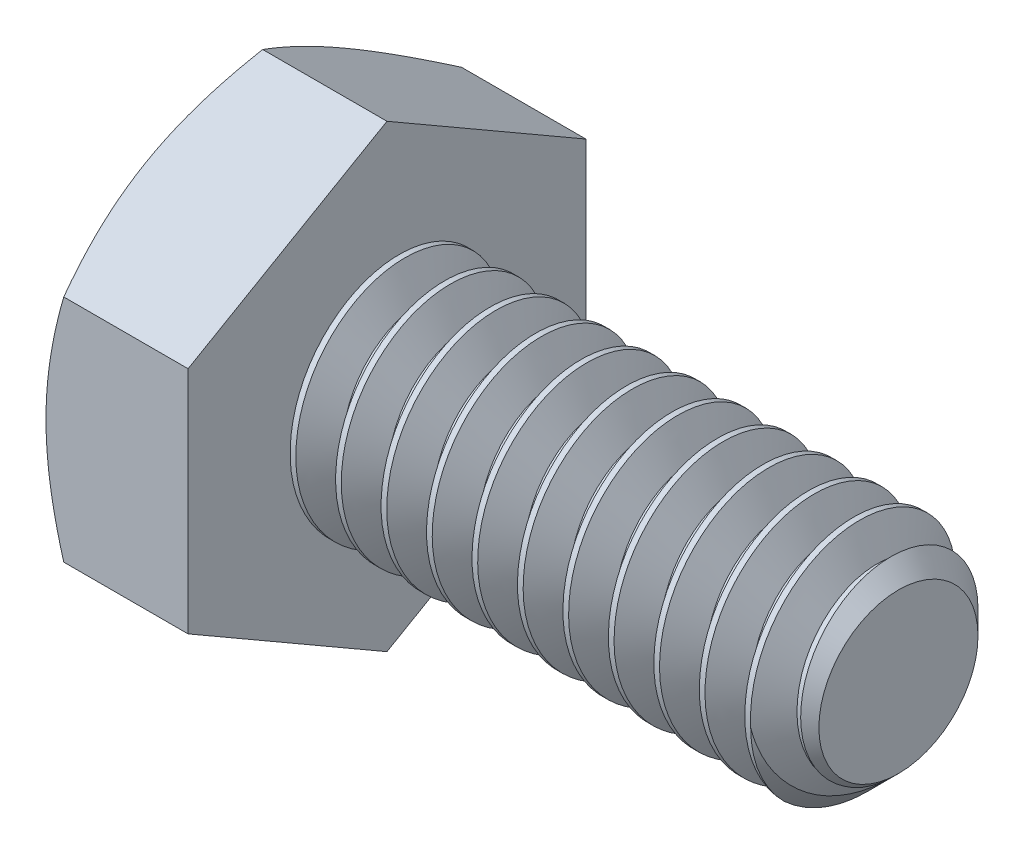
SolidWorks part; units mm, degrees
ref_plane "Front Plane" through (0, 0, 0) normal (0, 0, 1) x (1, 0, 0)
ref_plane "Top Plane" through (0, 0, 0) normal (0, 1, 0) x (1, 0, 0)
ref_plane "Right Plane" through (0, 0, 0) normal (1, 0, 0) x (0, 0, -1)
sketch "Sketch1" plane through (0, 0, 0) normal (0, 0, 1) x (1, 0, 0)
  line L0 (-9.1281, 0) -> (9.1281, 0) construction
  line L1 (9.1281, 3.175) -> (9.1281, -3.175) construction
  line L2 (-5.1594, 5.5562) -> (-5.1594, -5.5562) construction
  line L3 (-9.1281, 5.5562) -> (-9.1281, -5.5562) construction
  point P9 (-5.1594, 0)
  point P10 (4.6831, -3.175)
  dimension "D1" = 4.445
  dimension "Screw Dia" = 6.35
  dimension "Hex" = 11.1125
  dimension "Head Ht" = 3.9688
  dimension "Screw Lenght" = 14.2875
ref_plane "Plane2" through (9.1281, 0, 0) normal (1, 0, 0) x (0, 0, -1)
sketch "Sketch5" plane through (9.1281, 0, 0) normal (1, 0, 0) x (0, 0, -1)
  circle A0 centre (0, 0) radius 3.175
extrude "Boss-Extrude3" add sketch "Sketch5" against normal up to vertex (14.2875 mm away) up to point (-5.1594, 0, 0)
sketch "Sketch9" plane through (9.1281, 0, 0) normal (1, 0, 0) x (0, 0, -1)
  circle A1 centre (0, 0) radius 3.175
  circle A2 centre (0, 0) radius 3.175
  dimension "D1" = 0
curve "Helix/Spiral1" pitch 1.27 height 15.5575 turns 12.25 parameters "Pitch"=1.27
chamfer "Chamfer1" distance 0.9525 angle 45 1 edges at (9.1281, 0, -3.175)
sketch "Sketch10" plane through (0, 0, 0) normal (0, 0, 1) x (1, 0, 0)
  line L0 (9.1281, 3.175) -> (9.6044, 2.3501)
  line L1 (9.6044, 2.3501) -> (9.7631, 2.3501)
  line L2 (9.7631, 2.3501) -> (10.2394, 3.175)
  line L3 (9.1281, 3.175) -> (10.2394, 3.175)
  line L4 (9.6837, 3.175) -> (9.6837, 2.3501) construction
  line L5 (9.3663, 2.7626) -> (10.0013, 2.7626) construction
  dimension "D1" = 60
  dimension "D2" = 0.1588
  dimension "D3" = 0.635
sweep "Cut-Sweep1" cut profiles "Sketch10" path "Helix/Spiral1"
sketch "Sketch6" plane through (-5.1594, 0, 0) normal (-1, 0, 0) x (0, 0, 1)
  line L0 (0, 5.5562) -> (0, -5.5562) construction
  line L1 (5.5562, 3.2079) -> (0, 6.4158)
  line L2 (0, 6.4158) -> (-5.5562, 3.2079)
  line L3 (-5.5562, 3.2079) -> (-5.5562, -3.2079)
  line L4 (-5.5562, -3.2079) -> (0, -6.4158)
  line L5 (0, -6.4158) -> (5.5562, -3.2079)
  line L6 (5.5562, -3.2079) -> (5.5562, 3.2079)
  circle A0 centre (0, 0) radius 5.5562 construction
extrude "Boss-Extrude4" add sketch "Sketch6" along normal up to vertex (3.9688 mm away) up to point (-9.1281, -5.5562, 0)
sketch "Sketch7" plane through (-9.1281, 0, 0) normal (-1, 0, 0) x (0, 0, 1)
  circle A0 centre (0, 0) radius 5.5562 construction
  circle A1 centre (0, 0) radius 5.5562
sketch "Sketch8" plane through (-9.1281, 0, 0) normal (-1, 0, 0) x (0, 0, 1)
  circle A0 centre (0, 0) radius 5.5562 construction
  circle A1 centre (0, 0) radius 5.5562
extrude "Cut-Extrude3" cut sketch "Sketch8" against normal through all draft 60 flip side to cut
equation "\"D2@Sketch10\" = \"Pitch@Helix/Spiral1\"*.125"
equation "\"D3@Sketch10\" = \"Pitch@Helix/Spiral1\"*.5"
equation "\"D3@Helix/Spiral1\" = \"Screw Lenght@Sketch1\"+\"Pitch@Helix/Spiral1\""
equation "\"D1@Chamfer1\" = \"Pitch@Helix/Spiral1\"*.75"
equation "\"D1@Sketch1\" = \"Pitch@Helix/Spiral1\"*3.5"
